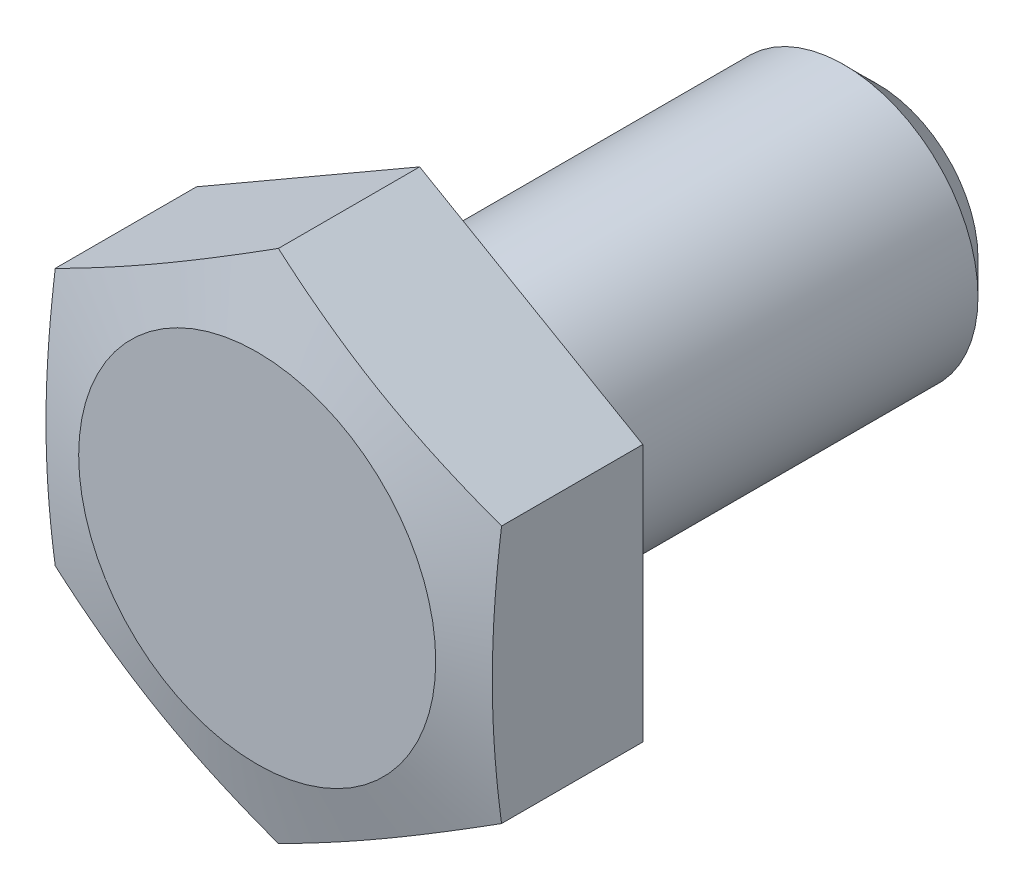
SolidWorks part; units mm, degrees
ref_plane "前视基准面" through (0, 0, 0) normal (0, 0, 1) x (1, 0, 0)
ref_plane "上视基准面" through (0, 0, 0) normal (0, 1, 0) x (1, 0, 0)
ref_plane "右视基准面" through (0, 0, 0) normal (1, 0, 0) x (0, 0, -1)
sketch "草图1" plane through (0, 0, 0) normal (0, 0, 1) x (1, 0, 0)
  line L1 (0, 5.7735) -> (-5, 2.8868)
  line L2 (-5, 2.8868) -> (-5, -2.8868)
  line L3 (-5, -2.8868) -> (0, -5.7735)
  line L4 (0, -5.7735) -> (5, -2.8868)
  line L5 (5, -2.8868) -> (5, 2.8868)
  line L6 (5, 2.8868) -> (0, 5.7735)
  circle A0 centre (0, 0) radius 5 construction
  dimension "s" = 10
extrude "凸台-拉伸1" add sketch "草图1" along normal blind 3.9
sketch "草图2" plane through (0, 0, 0) normal (0, 0, 1) x (1, 0, 0)
  circle A0 centre (0, 0) radius 4.5
  dimension "D1" = 9
ref_axis "基准轴1" through (0, 0, 0) along (0, 0, -1)
sketch "草图3" plane through (0, 0, 0) normal (0, 0, 1) x (1, 0, 0)
  circle A0 centre (0, 0) radius 3
  dimension "d" = 6
extrude "凸台-拉伸3" add sketch "草图3" against normal blind 10
cosmetic thread "装饰螺纹线1" parameters "D2"=2.459
sketch "草图4" plane through (0, 0, 0) normal (1, 0, 0) x (0, 0, -1)
  line L0 (2.242, 0) -> (-1.4572, 0) construction
  line L2 (-3.9, 20) -> (-3.9, 4)
  line L3 (-3.9, 20) -> (0.3872, 20)
  line L6 (-3.9, 2.8868) -> (-3.9, 5.7735) construction
  line L7 (-3.9, 4) -> (0.3872, 20)
  dimension "D3" = 20
  dimension "D2" = 4
  dimension "D1" = 15
revolve "切除-旋转1" cut sketch "草图4" angle 360 about L0
chamfer "倒角1" distance 0.75 angle 45 1 edges at (3, 0, -10)
extrude "切除-拉伸1" cut sketch "草图2" along normal blind 0.26 flip side to cut contours A0
fillet "圆角1" radius 0.1 1 edges at (3, 0, 0)
ref_plane "基准面1" through (0, 0, 0) normal (0, 0, -1) x (-1, 0, 0)
equation "\"D2@草图4\"=\"s@草图1\" * 0.4"
equation "\"D3@草图4\"=\"s@草图1\" * 2"
equation "\"D1@倒角1\"=\"d@草图3\" / 8"
equation "\"D1@草图2\"=\"s@草图1\"*0.9"
equation "\"D1@切除-拉伸1\" = \"k@凸台-拉伸1\" / 15"
